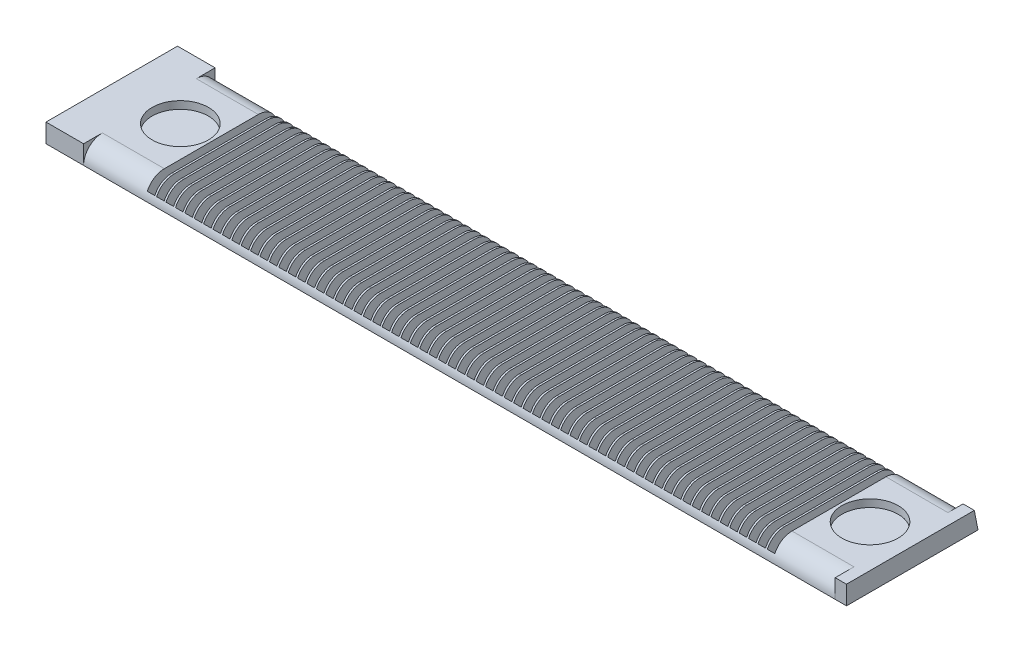
SolidWorks part; units mm, degrees
ref_plane "Front Plane" through (0, 0, 0) normal (0, 0, 1) x (1, 0, 0)
ref_plane "Top Plane" through (0, 0, 0) normal (0, 1, 0) x (1, 0, 0)
ref_plane "Right Plane" through (0, 0, 0) normal (1, 0, 0) x (0, 0, -1)
sketch "Sketch1" plane through (0, 0, 0) normal (0, 1, 0) x (1, 0, 0)
  line L0 (0, -42.6728) -> (0, 29.0893) construction
  line L1 (-100, 17.5) -> (100, 17.5)
  line L2 (-100, 17.5) -> (-100, -17.5)
  line L3 (-100, -17.5) -> (100, -17.5)
  line L4 (100, 17.5) -> (100, -17.5)
  line L5 (-100, 17.5) -> (100, -17.5) construction
  line L6 (-100, -17.5) -> (100, 17.5) construction
  point P0 (0, 0)
  dimension "D1" = 200
  dimension "D2" = 35
extrude "Boss-Extrude4" add sketch "Sketch1" along normal blind 5
fillet "Fillet1" radius 5 1 edges at (0, 5, -17.5) type face fillet first side face at (0, 5, 0) second side face at (0, 2.5, -17.5)
fillet "Fillet2" radius 5 1 edges at (0, 5, 17.5) type face fillet first side face at (0, 5, 2.5) second side face at (0, 2.5, 17.5)
sketch "Sketch5" plane through (0, 5, 0) normal (0, 1, 0) x (1, 0, 0)
  line L0 (0, -32.1337) -> (0, 31.2177) construction
  circle A0 centre (-91.7646, 0) radius 7.5
  circle A1 centre (91.7646, 0) radius 7.5
  dimension "D1" = 15
extrude "Cut-Extrude3" cut sketch "Sketch5" against normal blind 2
sketch "Sketch6" plane through (0, 5, 0) normal (0, 1, 0) x (1, 0, 0)
  line L0 (3.5, -17.0524) -> (3.5, 17.2933)
  line L1 (1, -17.0524) -> (1, 17.2933)
  line L2 (-1, -17.0524) -> (-1, 17.2933)
  line L3 (-1, 17.2933) -> (1, 17.2933)
  line L4 (-1, -17.0524) -> (1, -17.0524)
  line L5 (1.5, -17.0524) -> (1.5, 17.2933)
  line L6 (1.5, -17.0524) -> (3.5, -17.0524)
  line L7 (1.5, 17.2933) -> (3.5, 17.2933)
  line L8 (6, -17.0524) -> (6, 17.2933)
  line L9 (4, -17.0524) -> (4, 17.2933)
  line L10 (4, -17.0524) -> (6, -17.0524)
  line L11 (4, 17.2933) -> (6, 17.2933)
  line L12 (8.5, -17.0524) -> (8.5, 17.2933)
  line L13 (6.5, -17.0524) -> (6.5, 17.2933)
  line L14 (6.5, -17.0524) -> (8.5, -17.0524)
  line L15 (6.5, 17.2933) -> (8.5, 17.2933)
  line L16 (11, -17.0524) -> (11, 17.2933)
  line L17 (9, -17.0524) -> (9, 17.2933)
  line L18 (9, -17.0524) -> (11, -17.0524)
  line L19 (9, 17.2933) -> (11, 17.2933)
  line L20 (13.5, -17.0524) -> (13.5, 17.2933)
  line L21 (11.5, -17.0524) -> (11.5, 17.2933)
  line L22 (11.5, -17.0524) -> (13.5, -17.0524)
  line L23 (11.5, 17.2933) -> (13.5, 17.2933)
  line L24 (16, -17.0524) -> (16, 17.2933)
  line L25 (14, -17.0524) -> (14, 17.2933)
  line L26 (14, -17.0524) -> (16, -17.0524)
  line L27 (14, 17.2933) -> (16, 17.2933)
  line L28 (18.5, -17.0524) -> (18.5, 17.2933)
  line L29 (16.5, -17.0524) -> (16.5, 17.2933)
  line L30 (16.5, -17.0524) -> (18.5, -17.0524)
  line L31 (16.5, 17.2933) -> (18.5, 17.2933)
  line L32 (21, -17.0524) -> (21, 17.2933)
  line L33 (19, -17.0524) -> (19, 17.2933)
  line L34 (19, -17.0524) -> (21, -17.0524)
  line L35 (19, 17.2933) -> (21, 17.2933)
  line L36 (23.5, -17.0524) -> (23.5, 17.2933)
  line L37 (21.5, -17.0524) -> (21.5, 17.2933)
  line L38 (21.5, -17.0524) -> (23.5, -17.0524)
  line L39 (21.5, 17.2933) -> (23.5, 17.2933)
  line L40 (26, -17.0524) -> (26, 17.2933)
  line L41 (24, -17.0524) -> (24, 17.2933)
  line L42 (24, -17.0524) -> (26, -17.0524)
  line L43 (24, 17.2933) -> (26, 17.2933)
  line L44 (28.5, -17.0524) -> (28.5, 17.2933)
  line L45 (26.5, -17.0524) -> (26.5, 17.2933)
  line L46 (26.5, -17.0524) -> (28.5, -17.0524)
  line L47 (26.5, 17.2933) -> (28.5, 17.2933)
  line L48 (31, -17.0524) -> (31, 17.2933)
  line L49 (29, -17.0524) -> (29, 17.2933)
  line L50 (29, -17.0524) -> (31, -17.0524)
  line L51 (29, 17.2933) -> (31, 17.2933)
  line L52 (33.5, -17.0524) -> (33.5, 17.2933)
  line L53 (31.5, -17.0524) -> (31.5, 17.2933)
  line L54 (31.5, -17.0524) -> (33.5, -17.0524)
  line L55 (31.5, 17.2933) -> (33.5, 17.2933)
  line L56 (36, -17.0524) -> (36, 17.2933)
  line L57 (34, -17.0524) -> (34, 17.2933)
  line L58 (34, -17.0524) -> (36, -17.0524)
  line L59 (34, 17.2933) -> (36, 17.2933)
  line L60 (38.5, -17.0524) -> (38.5, 17.2933)
  line L61 (36.5, -17.0524) -> (36.5, 17.2933)
  line L62 (36.5, -17.0524) -> (38.5, -17.0524)
  line L63 (36.5, 17.2933) -> (38.5, 17.2933)
  line L64 (41, -17.0524) -> (41, 17.2933)
  line L65 (39, -17.0524) -> (39, 17.2933)
  line L66 (39, -17.0524) -> (41, -17.0524)
  line L67 (39, 17.2933) -> (41, 17.2933)
  line L68 (43.5, -17.0524) -> (43.5, 17.2933)
  line L69 (41.5, -17.0524) -> (41.5, 17.2933)
  line L70 (41.5, -17.0524) -> (43.5, -17.0524)
  line L71 (41.5, 17.2933) -> (43.5, 17.2933)
  line L72 (46, -17.0524) -> (46, 17.2933)
  line L73 (44, -17.0524) -> (44, 17.2933)
  line L74 (44, -17.0524) -> (46, -17.0524)
  line L75 (44, 17.2933) -> (46, 17.2933)
  line L76 (48.5, -17.0524) -> (48.5, 17.2933)
  line L77 (46.5, -17.0524) -> (46.5, 17.2933)
  line L78 (46.5, -17.0524) -> (48.5, -17.0524)
  line L79 (46.5, 17.2933) -> (48.5, 17.2933)
  line L80 (51, -17.0524) -> (51, 17.2933)
  line L81 (49, -17.0524) -> (49, 17.2933)
  line L82 (49, -17.0524) -> (51, -17.0524)
  line L83 (49, 17.2933) -> (51, 17.2933)
  line L84 (53.5, -17.0524) -> (53.5, 17.2933)
  line L85 (51.5, -17.0524) -> (51.5, 17.2933)
  line L86 (51.5, -17.0524) -> (53.5, -17.0524)
  line L87 (51.5, 17.2933) -> (53.5, 17.2933)
  line L88 (56, -17.0524) -> (56, 17.2933)
  line L89 (54, -17.0524) -> (54, 17.2933)
  line L90 (54, -17.0524) -> (56, -17.0524)
  line L91 (54, 17.2933) -> (56, 17.2933)
  line L92 (58.5, -17.0524) -> (58.5, 17.2933)
  line L93 (56.5, -17.0524) -> (56.5, 17.2933)
  line L94 (56.5, -17.0524) -> (58.5, -17.0524)
  line L95 (56.5, 17.2933) -> (58.5, 17.2933)
  line L96 (61, -17.0524) -> (61, 17.2933)
  line L97 (59, -17.0524) -> (59, 17.2933)
  line L98 (59, -17.0524) -> (61, -17.0524)
  line L99 (59, 17.2933) -> (61, 17.2933)
  line L100 (63.5, -17.0524) -> (63.5, 17.2933)
  line L101 (61.5, -17.0524) -> (61.5, 17.2933)
  line L102 (61.5, -17.0524) -> (63.5, -17.0524)
  line L103 (61.5, 17.2933) -> (63.5, 17.2933)
  line L104 (66, -17.0524) -> (66, 17.2933)
  line L105 (64, -17.0524) -> (64, 17.2933)
  line L106 (64, -17.0524) -> (66, -17.0524)
  line L107 (64, 17.2933) -> (66, 17.2933)
  line L108 (68.5, -17.0524) -> (68.5, 17.2933)
  line L109 (66.5, -17.0524) -> (66.5, 17.2933)
  line L110 (66.5, -17.0524) -> (68.5, -17.0524)
  line L111 (66.5, 17.2933) -> (68.5, 17.2933)
  line L112 (71, -17.0524) -> (71, 17.2933)
  line L113 (69, -17.0524) -> (69, 17.2933)
  line L114 (69, -17.0524) -> (71, -17.0524)
  line L115 (69, 17.2933) -> (71, 17.2933)
  line L116 (73.5, -17.0524) -> (73.5, 17.2933)
  line L117 (71.5, -17.0524) -> (71.5, 17.2933)
  line L118 (71.5, -17.0524) -> (73.5, -17.0524)
  line L119 (71.5, 17.2933) -> (73.5, 17.2933)
  line L120 (76, -17.0524) -> (76, 17.2933)
  line L121 (74, -17.0524) -> (74, 17.2933)
  line L122 (74, -17.0524) -> (76, -17.0524)
  line L123 (74, 17.2933) -> (76, 17.2933)
  line L124 (78.5, -17.0524) -> (78.5, 17.2933)
  line L125 (76.5, -17.0524) -> (76.5, 17.2933)
  line L126 (76.5, -17.0524) -> (78.5, -17.0524)
  line L127 (76.5, 17.2933) -> (78.5, 17.2933)
  line L128 (81, -17.0524) -> (81, 17.2933)
  line L129 (79, -17.0524) -> (79, 17.2933)
  line L130 (79, -17.0524) -> (81, -17.0524)
  line L131 (79, 17.2933) -> (81, 17.2933)
  line L132 (83.5, -17.0524) -> (83.5, 17.2933)
  line L133 (81.5, -17.0524) -> (81.5, 17.2933)
  line L134 (81.5, -17.0524) -> (83.5, -17.0524)
  line L135 (81.5, 17.2933) -> (83.5, 17.2933)
  line L136 (1, -17.0524) -> (3.5, -17.0524) construction
  line L137 (-3.5, -17.0524) -> (-3.5, 17.2933)
  line L138 (-1.5, -17.0524) -> (-1.5, 17.2933)
  line L139 (-3.5, -17.0524) -> (-1.5, -17.0524)
  line L140 (-3.5, 17.2933) -> (-1.5, 17.2933)
  line L141 (-6, -17.0524) -> (-6, 17.2933)
  line L142 (-4, -17.0524) -> (-4, 17.2933)
  line L143 (-6, -17.0524) -> (-4, -17.0524)
  line L144 (-6, 17.2933) -> (-4, 17.2933)
  line L145 (-8.5, -17.0524) -> (-8.5, 17.2933)
  line L146 (-6.5, -17.0524) -> (-6.5, 17.2933)
  line L147 (-8.5, -17.0524) -> (-6.5, -17.0524)
  line L148 (-8.5, 17.2933) -> (-6.5, 17.2933)
  line L149 (-11, -17.0524) -> (-11, 17.2933)
  line L150 (-9, -17.0524) -> (-9, 17.2933)
  line L151 (-11, -17.0524) -> (-9, -17.0524)
  line L152 (-11, 17.2933) -> (-9, 17.2933)
  line L153 (-13.5, -17.0524) -> (-13.5, 17.2933)
  line L154 (-11.5, -17.0524) -> (-11.5, 17.2933)
  line L155 (-13.5, -17.0524) -> (-11.5, -17.0524)
  line L156 (-13.5, 17.2933) -> (-11.5, 17.2933)
  line L157 (-16, -17.0524) -> (-16, 17.2933)
  line L158 (-14, -17.0524) -> (-14, 17.2933)
  line L159 (-16, -17.0524) -> (-14, -17.0524)
  line L160 (-16, 17.2933) -> (-14, 17.2933)
  line L161 (-18.5, -17.0524) -> (-18.5, 17.2933)
  line L162 (-16.5, -17.0524) -> (-16.5, 17.2933)
  line L163 (-18.5, -17.0524) -> (-16.5, -17.0524)
  line L164 (-18.5, 17.2933) -> (-16.5, 17.2933)
  line L165 (-21, -17.0524) -> (-21, 17.2933)
  line L166 (-19, -17.0524) -> (-19, 17.2933)
  line L167 (-21, -17.0524) -> (-19, -17.0524)
  line L168 (-21, 17.2933) -> (-19, 17.2933)
  line L169 (-23.5, -17.0524) -> (-23.5, 17.2933)
  line L170 (-21.5, -17.0524) -> (-21.5, 17.2933)
  line L171 (-23.5, -17.0524) -> (-21.5, -17.0524)
  line L172 (-23.5, 17.2933) -> (-21.5, 17.2933)
  line L173 (-26, -17.0524) -> (-26, 17.2933)
  line L174 (-24, -17.0524) -> (-24, 17.2933)
  line L175 (-26, -17.0524) -> (-24, -17.0524)
  line L176 (-26, 17.2933) -> (-24, 17.2933)
  line L177 (-28.5, -17.0524) -> (-28.5, 17.2933)
  line L178 (-26.5, -17.0524) -> (-26.5, 17.2933)
  line L179 (-28.5, -17.0524) -> (-26.5, -17.0524)
  line L180 (-28.5, 17.2933) -> (-26.5, 17.2933)
  line L181 (-31, -17.0524) -> (-31, 17.2933)
  line L182 (-29, -17.0524) -> (-29, 17.2933)
  line L183 (-31, -17.0524) -> (-29, -17.0524)
  line L184 (-31, 17.2933) -> (-29, 17.2933)
  line L185 (-33.5, -17.0524) -> (-33.5, 17.2933)
  line L186 (-31.5, -17.0524) -> (-31.5, 17.2933)
  line L187 (-33.5, -17.0524) -> (-31.5, -17.0524)
  line L188 (-33.5, 17.2933) -> (-31.5, 17.2933)
  line L189 (-36, -17.0524) -> (-36, 17.2933)
  line L190 (-34, -17.0524) -> (-34, 17.2933)
  line L191 (-36, -17.0524) -> (-34, -17.0524)
  line L192 (-36, 17.2933) -> (-34, 17.2933)
  line L193 (-38.5, -17.0524) -> (-38.5, 17.2933)
  line L194 (-36.5, -17.0524) -> (-36.5, 17.2933)
  line L195 (-38.5, -17.0524) -> (-36.5, -17.0524)
  line L196 (-38.5, 17.2933) -> (-36.5, 17.2933)
  line L197 (-41, -17.0524) -> (-41, 17.2933)
  line L198 (-39, -17.0524) -> (-39, 17.2933)
  line L199 (-41, -17.0524) -> (-39, -17.0524)
  line L200 (-41, 17.2933) -> (-39, 17.2933)
  line L201 (-43.5, -17.0524) -> (-43.5, 17.2933)
  line L202 (-41.5, -17.0524) -> (-41.5, 17.2933)
  line L203 (-43.5, -17.0524) -> (-41.5, -17.0524)
  line L204 (-43.5, 17.2933) -> (-41.5, 17.2933)
  line L205 (-46, -17.0524) -> (-46, 17.2933)
  line L206 (-44, -17.0524) -> (-44, 17.2933)
  line L207 (-46, -17.0524) -> (-44, -17.0524)
  line L208 (-46, 17.2933) -> (-44, 17.2933)
  line L209 (-48.5, -17.0524) -> (-48.5, 17.2933)
  line L210 (-46.5, -17.0524) -> (-46.5, 17.2933)
  line L211 (-48.5, -17.0524) -> (-46.5, -17.0524)
  line L212 (-48.5, 17.2933) -> (-46.5, 17.2933)
  line L213 (-51, -17.0524) -> (-51, 17.2933)
  line L214 (-49, -17.0524) -> (-49, 17.2933)
  line L215 (-51, -17.0524) -> (-49, -17.0524)
  line L216 (-51, 17.2933) -> (-49, 17.2933)
  line L217 (-53.5, -17.0524) -> (-53.5, 17.2933)
  line L218 (-51.5, -17.0524) -> (-51.5, 17.2933)
  line L219 (-53.5, -17.0524) -> (-51.5, -17.0524)
  line L220 (-53.5, 17.2933) -> (-51.5, 17.2933)
  line L221 (-56, -17.0524) -> (-56, 17.2933)
  line L222 (-54, -17.0524) -> (-54, 17.2933)
  line L223 (-56, -17.0524) -> (-54, -17.0524)
  line L224 (-56, 17.2933) -> (-54, 17.2933)
  line L225 (-58.5, -17.0524) -> (-58.5, 17.2933)
  line L226 (-56.5, -17.0524) -> (-56.5, 17.2933)
  line L227 (-58.5, -17.0524) -> (-56.5, -17.0524)
  line L228 (-58.5, 17.2933) -> (-56.5, 17.2933)
  line L229 (-61, -17.0524) -> (-61, 17.2933)
  line L230 (-59, -17.0524) -> (-59, 17.2933)
  line L231 (-61, -17.0524) -> (-59, -17.0524)
  line L232 (-61, 17.2933) -> (-59, 17.2933)
  line L233 (-63.5, -17.0524) -> (-63.5, 17.2933)
  line L234 (-61.5, -17.0524) -> (-61.5, 17.2933)
  line L235 (-63.5, -17.0524) -> (-61.5, -17.0524)
  line L236 (-63.5, 17.2933) -> (-61.5, 17.2933)
  line L237 (-66, -17.0524) -> (-66, 17.2933)
  line L238 (-64, -17.0524) -> (-64, 17.2933)
  line L239 (-66, -17.0524) -> (-64, -17.0524)
  line L240 (-66, 17.2933) -> (-64, 17.2933)
  line L241 (-68.5, -17.0524) -> (-68.5, 17.2933)
  line L242 (-66.5, -17.0524) -> (-66.5, 17.2933)
  line L243 (-68.5, -17.0524) -> (-66.5, -17.0524)
  line L244 (-68.5, 17.2933) -> (-66.5, 17.2933)
  line L245 (-71, -17.0524) -> (-71, 17.2933)
  line L246 (-69, -17.0524) -> (-69, 17.2933)
  line L247 (-71, -17.0524) -> (-69, -17.0524)
  line L248 (-71, 17.2933) -> (-69, 17.2933)
  line L249 (-73.5, -17.0524) -> (-73.5, 17.2933)
  line L250 (-71.5, -17.0524) -> (-71.5, 17.2933)
  line L251 (-73.5, -17.0524) -> (-71.5, -17.0524)
  line L252 (-73.5, 17.2933) -> (-71.5, 17.2933)
  line L253 (-76, -17.0524) -> (-76, 17.2933)
  line L254 (-74, -17.0524) -> (-74, 17.2933)
  line L255 (-76, -17.0524) -> (-74, -17.0524)
  line L256 (-76, 17.2933) -> (-74, 17.2933)
  line L257 (-78.5, -17.0524) -> (-78.5, 17.2933)
  line L258 (-76.5, -17.0524) -> (-76.5, 17.2933)
  line L259 (-78.5, -17.0524) -> (-76.5, -17.0524)
  line L260 (-78.5, 17.2933) -> (-76.5, 17.2933)
  line L261 (-81, -17.0524) -> (-81, 17.2933)
  line L262 (-79, -17.0524) -> (-79, 17.2933)
  line L263 (-81, -17.0524) -> (-79, -17.0524)
  line L264 (-81, 17.2933) -> (-79, 17.2933)
  line L265 (-83.5, -17.0524) -> (-83.5, 17.2933)
  line L266 (-81.5, -17.0524) -> (-81.5, 17.2933)
  line L267 (-83.5, -17.0524) -> (-81.5, -17.0524)
  line L268 (-83.5, 17.2933) -> (-81.5, 17.2933)
  line L269 (-1, -17.0524) -> (-3.5, -17.0524) construction
  point P0 (0, -18.8927)
  point P1 (0, 17.2933)
  point P3 (1, -18.8927)
  point P5 (-1, -18.8927)
  dimension "D2" = 2.5
  dimension "D4" = 2.5
  dimension "D1" = 34
  dimension "D3" = 34
extrude "Cut-Extrude4" cut sketch "Sketch6" against normal through all
sketch "Sketch7" plane through (0, 0, 0) normal (0, 1, 0) x (1, 0, 0)
  line L1 (-100, 17.5) -> (-100, -17.5)
extrude "Extrude-Thin1" add sketch "Sketch7" along normal blind 5 thin thin type one direction wall 10
sketch "Sketch8" plane through (100, 0, 0) normal (1, 0, 0) x (0, 0, -1)
  line L0 (-17.5, 0) -> (17.5, 0)
  line L1 (-17.5, 0) -> (-17.5, 5)
  line L2 (-17.5, 5) -> (15.1866, 5)
  line L3 (17.5, 0) -> (16.5207, 5)
  line L4 (16.5207, 5) -> (15.1866, 5)
extrude "Boss-Extrude7" add sketch "Sketch8" along normal blind 3
